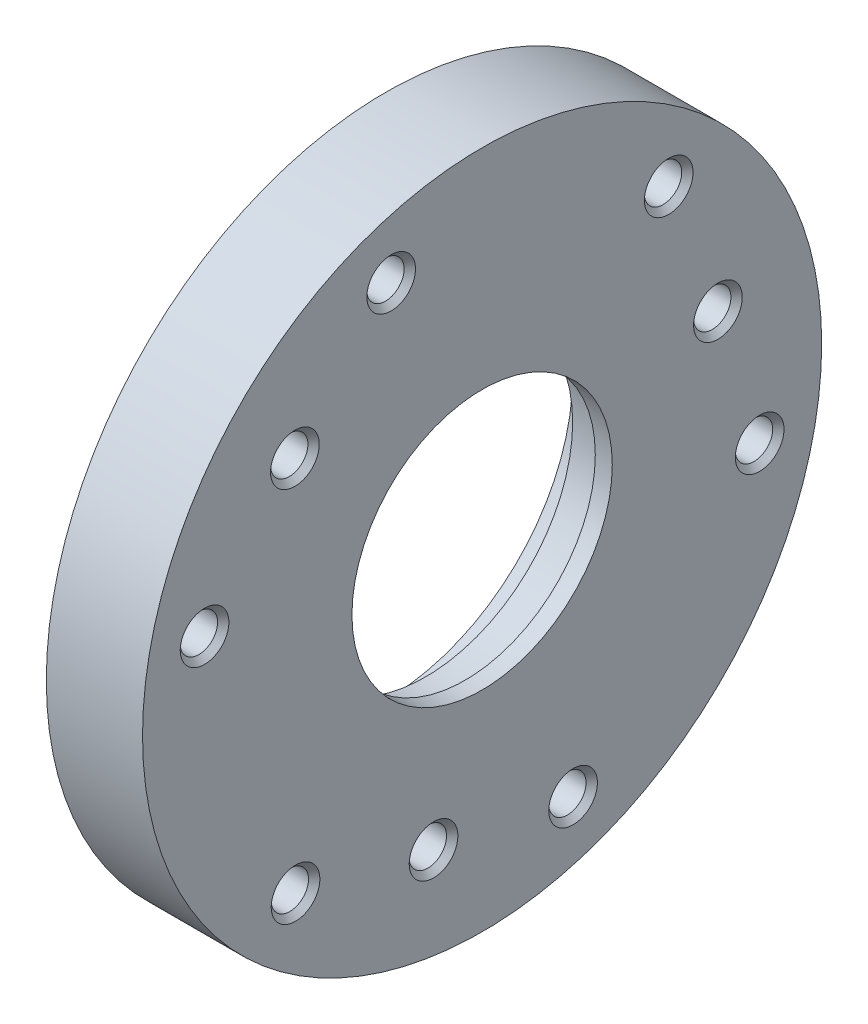
SolidWorks part; units mm, degrees
ref_plane "Front Plane" through (0, 0, 0) normal (0, 0, 1) x (1, 0, 0)
ref_plane "Top Plane" through (0, 0, 0) normal (0, 1, 0) x (1, 0, 0)
ref_plane "Right Plane" through (0, 0, 0) normal (1, 0, 0) x (0, 0, -1)
sketch "Sketch1" plane through (0, 0, 0) normal (0, 0, 1) x (1, 0, 0)
  line L0 (0, 0) -> (14, 0) construction
  line L1 (0, 60) -> (0, 33)
  line L2 (0, 33) -> (7, 33)
  line L3 (7, 33) -> (7, 26)
  line L4 (7, 26) -> (14, 26)
  line L5 (14, 26) -> (14, 23)
  line L6 (14, 23) -> (17, 23)
  line L7 (17, 23) -> (17, 60)
  line L8 (17, 60) -> (0, 60)
  dimension "D1" = 17
  dimension "D2" = 26
  dimension "D3" = 7
  dimension "D4" = 3
  dimension "D5" = 60
  dimension "D6" = 33
  dimension "D7" = 3
revolve "Revolve1" add sketch "Sketch1" angle 360 about L0
sketch "Sketch2" plane through (0, 0, 0) normal (-1, 0, 0) x (0, 0, 1)
  circle A0 centre (0, 0) radius 40 construction
  circle A1 centre (0, 40) radius 2.5
  circle A2 centre (15.3073, 36.9552) radius 2.5
  circle A3 centre (28.2843, 28.2843) radius 2.5
  circle A4 centre (36.9552, 15.3073) radius 2.5
  circle A5 centre (40, 0) radius 2.5
  circle A6 centre (36.9552, -15.3073) radius 2.5
  circle A7 centre (28.2843, -28.2843) radius 2.5
  circle A8 centre (15.3073, -36.9552) radius 2.5
  circle A9 centre (0, -40) radius 2.5
  circle A10 centre (-15.3073, -36.9552) radius 2.5
  circle A11 centre (-28.2843, -28.2843) radius 2.5
  circle A12 centre (-36.9552, -15.3073) radius 2.5
  circle A13 centre (-40, 0) radius 2.5
  circle A14 centre (-36.9552, 15.3073) radius 2.5
  circle A15 centre (-28.2843, 28.2843) radius 2.5
  circle A16 centre (-15.3073, 36.9552) radius 2.5
  point P37 (0, 0)
  dimension "D1" = 80
  dimension "D2" = 5
  dimension "D3" = 16
extrude "Cut-Extrude1" cut sketch "Sketch2" against normal blind 4
sketch "Sketch3" plane through (17, 0, 0) normal (1, 0, 0) x (0, 0, -1)
  circle A0 centre (49.0393, -9.7545) radius 3
  circle A1 centre (16.072, -47.3465) radius 3
  circle A2 centre (-32.9673, -37.592) radius 3
  circle A3 centre (-49.0393, 9.7545) radius 3
  circle A4 centre (-16.072, 47.3465) radius 3
  circle A5 centre (32.9673, 37.592) radius 3
  point P20 (0, 0)
  dimension "D2" = 6
  dimension "D1" = 6
extrude "Cut-Extrude4" cut sketch "Sketch3" against normal through all
sketch "Sketch4" [suppressed] plane through (17, 0, 0) normal (1, 0, 0) x (0, 0, -1)
  circle A0 centre (32.9673, 37.592) radius 5.25
  circle A1 centre (49.0393, -9.7545) radius 5.25
  circle A2 centre (16.072, -47.3465) radius 5.25
  circle A3 centre (-32.9673, -37.592) radius 5.25
  circle A4 centre (-49.0393, 9.7545) radius 5.25
  circle A5 centre (-16.072, 47.3465) radius 5.25
  point P20 (0, 0)
  dimension "D1" = 10.5
  dimension "D2" = 6
extrude "Cut-Extrude5" [suppressed] cut sketch "Sketch4" against normal blind 4
sketch "Sketch5" plane through (17, 0, 0) normal (1, 0, 0) x (0, 0, -1)
  line L0 (32.9673, 37.592) -> (0, 0) construction
  line L1 (0, 0) -> (41.6649, 14.1433) construction
  circle A0 centre (32.9673, 37.592) radius 3.3
  circle A1 centre (49.0393, -9.7545) radius 3.3
  circle A2 centre (16.072, -47.3465) radius 3.3
  circle A3 centre (-32.9673, -37.592) radius 3.3
  circle A4 centre (-49.0393, 9.7545) radius 3.3
  circle A5 centre (-16.072, 47.3465) radius 3.3
  circle A8 centre (0, 0) radius 44 construction
  circle A9 centre (41.6649, 14.1433) radius 3.3
  circle A10 centre (-8.584, -43.1546) radius 3.3
  circle A11 centre (-33.081, 29.0112) radius 3.3
  point P19 (0, 0)
  point P24 (32.9673, 37.592)
  point P33 (0, 0)
  dimension "D1" = 6.6
  dimension "D4" = 88
  dimension "D5" = 30
  dimension "D2" = 6
  dimension "D3" = 3
extrude "Cut-Extrude6" cut sketch "Sketch5" against normal blind 10
chamfer "Chamfer1" distance 1 angle 45 9 edges at (17, 47.3465, 12.772) (17, 29.0112, 29.781) (17, 9.7545, 45.7393) (17, -37.592, 29.6673) (17, -43.1546, 5.284) (17, -47.3465, -19.372) (17, -9.7545, -52.3393) (17, 14.1433, -44.9649) (17, 37.592, -36.2673)
equation "\"R_ROLL\"= 5mm"
equation "\"D_SUN\"= 80mm"
equation "\"NUM_ROLL\"= 16"
equation "\"RHO\"= 1mm"
equation "\"D_SHAFT\"= 15mm"
equation "\"D_OUTPUT\"= 40mm"
equation "\"NUM_OUT\"= 6"
equation "\"R_OUT_ROLL\"= 5mm"
equation "\"D1@Sketch2\"=\"D_SUN\""
equation "\"D3@Sketch2\"=\"NUM_ROLL\""
